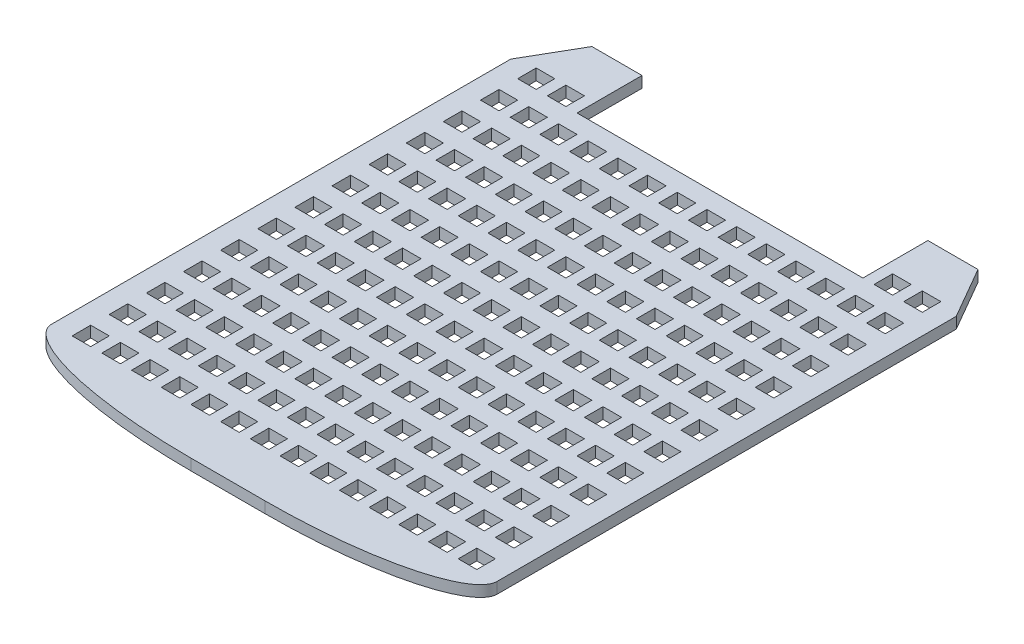
SolidWorks part; units mm, degrees
material "Balsa"
ref_plane "Front Plane" through (0, 0, 0) normal (0, 0, 1) x (1, 0, 0)
ref_plane "Top Plane" through (0, 0, 0) normal (0, 1, 0) x (1, 0, 0)
ref_plane "Right Plane" through (0, 0, 0) normal (1, 0, 0) x (0, 0, -1)
sketch "Sketch1" plane through (0, 0, 0) normal (0, 1, 0) x (1, 0, 0)
  line L1 (-60, 75) -> (60, 75)
  line L2 (-60, 75) -> (-60, -75)
  line L3 (-60, -75) -> (60, -75)
  line L4 (60, 75) -> (60, -75)
  line L5 (-60, 75) -> (60, -75) construction
  line L6 (-60, -75) -> (60, 75) construction
  point P0 (0, 0)
  dimension "D1" = 120
  dimension "D2" = 150
extrude "Boss-Extrude1" add sketch "Sketch1" along normal blind 3
sketch "Sketch2" plane through (0, 3, 0) normal (0, 1, 0) x (1, 0, 0)
  line L0 (-60, 75) -> (-60, -75) construction
  line L1 (-54.5, 62.5) -> (-49.5, 62.5)
  line L2 (-54.5, 62.5) -> (-54.5, 57.5)
  line L3 (-54.5, 57.5) -> (-49.5, 57.5)
  line L4 (-49.5, 62.5) -> (-49.5, 57.5)
  line L5 (-54.5, 62.5) -> (-49.5, 57.5) construction
  line L6 (-54.5, 57.5) -> (-49.5, 62.5) construction
  line L7 (60, 75) -> (-60, 75) construction
  line L8 (-46.5, 62.5) -> (-46.5, 57.5)
  line L9 (-46.5, 62.5) -> (-41.5, 62.5)
  line L10 (-41.5, 62.5) -> (-41.5, 57.5)
  line L11 (-46.5, 57.5) -> (-41.5, 57.5)
  line L12 (-38.5, 62.5) -> (-38.5, 57.5)
  line L13 (-38.5, 62.5) -> (-33.5, 62.5)
  line L14 (-33.5, 62.5) -> (-33.5, 57.5)
  line L15 (-38.5, 57.5) -> (-33.5, 57.5)
  line L16 (-30.5, 62.5) -> (-30.5, 57.5)
  line L17 (-30.5, 62.5) -> (-25.5, 62.5)
  line L18 (-25.5, 62.5) -> (-25.5, 57.5)
  line L19 (-30.5, 57.5) -> (-25.5, 57.5)
  line L20 (-22.5, 62.5) -> (-22.5, 57.5)
  line L21 (-22.5, 62.5) -> (-17.5, 62.5)
  line L22 (-17.5, 62.5) -> (-17.5, 57.5)
  line L23 (-22.5, 57.5) -> (-17.5, 57.5)
  line L24 (-14.5, 62.5) -> (-14.5, 57.5)
  line L25 (-14.5, 62.5) -> (-9.5, 62.5)
  line L26 (-9.5, 62.5) -> (-9.5, 57.5)
  line L27 (-14.5, 57.5) -> (-9.5, 57.5)
  line L28 (-6.5, 62.5) -> (-6.5, 57.5)
  line L29 (-6.5, 62.5) -> (-1.5, 62.5)
  line L30 (-1.5, 62.5) -> (-1.5, 57.5)
  line L31 (-6.5, 57.5) -> (-1.5, 57.5)
  line L32 (1.5, 62.5) -> (1.5, 57.5)
  line L33 (1.5, 62.5) -> (6.5, 62.5)
  line L34 (6.5, 62.5) -> (6.5, 57.5)
  line L35 (1.5, 57.5) -> (6.5, 57.5)
  line L36 (9.5, 62.5) -> (9.5, 57.5)
  line L37 (9.5, 62.5) -> (14.5, 62.5)
  line L38 (14.5, 62.5) -> (14.5, 57.5)
  line L39 (9.5, 57.5) -> (14.5, 57.5)
  line L40 (17.5, 62.5) -> (17.5, 57.5)
  line L41 (17.5, 62.5) -> (22.5, 62.5)
  line L42 (22.5, 62.5) -> (22.5, 57.5)
  line L43 (17.5, 57.5) -> (22.5, 57.5)
  line L44 (25.5, 62.5) -> (25.5, 57.5)
  line L45 (25.5, 62.5) -> (30.5, 62.5)
  line L46 (30.5, 62.5) -> (30.5, 57.5)
  line L47 (25.5, 57.5) -> (30.5, 57.5)
  line L48 (33.5, 62.5) -> (33.5, 57.5)
  line L49 (33.5, 62.5) -> (38.5, 62.5)
  line L50 (38.5, 62.5) -> (38.5, 57.5)
  line L51 (33.5, 57.5) -> (38.5, 57.5)
  line L52 (41.5, 62.5) -> (41.5, 57.5)
  line L53 (41.5, 62.5) -> (46.5, 62.5)
  line L54 (46.5, 62.5) -> (46.5, 57.5)
  line L55 (41.5, 57.5) -> (46.5, 57.5)
  line L56 (49.5, 62.5) -> (49.5, 57.5)
  line L57 (49.5, 62.5) -> (54.5, 62.5)
  line L58 (54.5, 62.5) -> (54.5, 57.5)
  line L59 (49.5, 57.5) -> (54.5, 57.5)
  line L60 (-46.5, 52.5) -> (-46.5, 47.5)
  line L61 (-46.5, 52.5) -> (-41.5, 52.5)
  line L62 (-41.5, 52.5) -> (-41.5, 47.5)
  line L63 (-46.5, 47.5) -> (-41.5, 47.5)
  line L64 (-38.5, 52.5) -> (-38.5, 47.5)
  line L65 (-38.5, 52.5) -> (-33.5, 52.5)
  line L66 (-33.5, 52.5) -> (-33.5, 47.5)
  line L67 (-38.5, 47.5) -> (-33.5, 47.5)
  line L68 (-30.5, 52.5) -> (-30.5, 47.5)
  line L69 (-30.5, 52.5) -> (-25.5, 52.5)
  line L70 (-25.5, 52.5) -> (-25.5, 47.5)
  line L71 (-30.5, 47.5) -> (-25.5, 47.5)
  line L72 (-22.5, 52.5) -> (-22.5, 47.5)
  line L73 (-22.5, 52.5) -> (-17.5, 52.5)
  line L74 (-17.5, 52.5) -> (-17.5, 47.5)
  line L75 (-22.5, 47.5) -> (-17.5, 47.5)
  line L76 (-14.5, 52.5) -> (-14.5, 47.5)
  line L77 (-14.5, 52.5) -> (-9.5, 52.5)
  line L78 (-9.5, 52.5) -> (-9.5, 47.5)
  line L79 (-14.5, 47.5) -> (-9.5, 47.5)
  line L80 (-6.5, 52.5) -> (-6.5, 47.5)
  line L81 (-6.5, 52.5) -> (-1.5, 52.5)
  line L82 (-1.5, 52.5) -> (-1.5, 47.5)
  line L83 (-6.5, 47.5) -> (-1.5, 47.5)
  line L84 (1.5, 52.5) -> (1.5, 47.5)
  line L85 (1.5, 52.5) -> (6.5, 52.5)
  line L86 (6.5, 52.5) -> (6.5, 47.5)
  line L87 (1.5, 47.5) -> (6.5, 47.5)
  line L88 (9.5, 52.5) -> (9.5, 47.5)
  line L89 (9.5, 52.5) -> (14.5, 52.5)
  line L90 (14.5, 52.5) -> (14.5, 47.5)
  line L91 (9.5, 47.5) -> (14.5, 47.5)
  line L92 (17.5, 52.5) -> (17.5, 47.5)
  line L93 (17.5, 52.5) -> (22.5, 52.5)
  line L94 (22.5, 52.5) -> (22.5, 47.5)
  line L95 (17.5, 47.5) -> (22.5, 47.5)
  line L96 (25.5, 52.5) -> (25.5, 47.5)
  line L97 (25.5, 52.5) -> (30.5, 52.5)
  line L98 (30.5, 52.5) -> (30.5, 47.5)
  line L99 (25.5, 47.5) -> (30.5, 47.5)
  line L100 (33.5, 52.5) -> (33.5, 47.5)
  line L101 (33.5, 52.5) -> (38.5, 52.5)
  line L102 (38.5, 52.5) -> (38.5, 47.5)
  line L103 (33.5, 47.5) -> (38.5, 47.5)
  line L104 (41.5, 52.5) -> (41.5, 47.5)
  line L105 (41.5, 52.5) -> (46.5, 52.5)
  line L106 (46.5, 52.5) -> (46.5, 47.5)
  line L107 (41.5, 47.5) -> (46.5, 47.5)
  line L108 (49.5, 52.5) -> (49.5, 47.5)
  line L109 (49.5, 52.5) -> (54.5, 52.5)
  line L110 (54.5, 52.5) -> (54.5, 47.5)
  line L111 (49.5, 47.5) -> (54.5, 47.5)
  line L112 (-46.5, 42.5) -> (-46.5, 37.5)
  line L113 (-46.5, 42.5) -> (-41.5, 42.5)
  line L114 (-41.5, 42.5) -> (-41.5, 37.5)
  line L115 (-46.5, 37.5) -> (-41.5, 37.5)
  line L116 (-38.5, 42.5) -> (-38.5, 37.5)
  line L117 (-38.5, 42.5) -> (-33.5, 42.5)
  line L118 (-33.5, 42.5) -> (-33.5, 37.5)
  line L119 (-38.5, 37.5) -> (-33.5, 37.5)
  line L120 (-30.5, 42.5) -> (-30.5, 37.5)
  line L121 (-30.5, 42.5) -> (-25.5, 42.5)
  line L122 (-25.5, 42.5) -> (-25.5, 37.5)
  line L123 (-30.5, 37.5) -> (-25.5, 37.5)
  line L124 (-22.5, 42.5) -> (-22.5, 37.5)
  line L125 (-22.5, 42.5) -> (-17.5, 42.5)
  line L126 (-17.5, 42.5) -> (-17.5, 37.5)
  line L127 (-22.5, 37.5) -> (-17.5, 37.5)
  line L128 (-14.5, 42.5) -> (-14.5, 37.5)
  line L129 (-14.5, 42.5) -> (-9.5, 42.5)
  line L130 (-9.5, 42.5) -> (-9.5, 37.5)
  line L131 (-14.5, 37.5) -> (-9.5, 37.5)
  line L132 (-6.5, 42.5) -> (-6.5, 37.5)
  line L133 (-6.5, 42.5) -> (-1.5, 42.5)
  line L134 (-1.5, 42.5) -> (-1.5, 37.5)
  line L135 (-6.5, 37.5) -> (-1.5, 37.5)
  line L136 (1.5, 42.5) -> (1.5, 37.5)
  line L137 (1.5, 42.5) -> (6.5, 42.5)
  line L138 (6.5, 42.5) -> (6.5, 37.5)
  line L139 (1.5, 37.5) -> (6.5, 37.5)
  line L140 (9.5, 42.5) -> (9.5, 37.5)
  line L141 (9.5, 42.5) -> (14.5, 42.5)
  line L142 (14.5, 42.5) -> (14.5, 37.5)
  line L143 (9.5, 37.5) -> (14.5, 37.5)
  line L144 (17.5, 42.5) -> (17.5, 37.5)
  line L145 (17.5, 42.5) -> (22.5, 42.5)
  line L146 (22.5, 42.5) -> (22.5, 37.5)
  line L147 (17.5, 37.5) -> (22.5, 37.5)
  line L148 (25.5, 42.5) -> (25.5, 37.5)
  line L149 (25.5, 42.5) -> (30.5, 42.5)
  line L150 (30.5, 42.5) -> (30.5, 37.5)
  line L151 (25.5, 37.5) -> (30.5, 37.5)
  line L152 (33.5, 42.5) -> (33.5, 37.5)
  line L153 (33.5, 42.5) -> (38.5, 42.5)
  line L154 (38.5, 42.5) -> (38.5, 37.5)
  line L155 (33.5, 37.5) -> (38.5, 37.5)
  line L156 (41.5, 42.5) -> (41.5, 37.5)
  line L157 (41.5, 42.5) -> (46.5, 42.5)
  line L158 (46.5, 42.5) -> (46.5, 37.5)
  line L159 (41.5, 37.5) -> (46.5, 37.5)
  line L160 (49.5, 42.5) -> (49.5, 37.5)
  line L161 (49.5, 42.5) -> (54.5, 42.5)
  line L162 (54.5, 42.5) -> (54.5, 37.5)
  line L163 (49.5, 37.5) -> (54.5, 37.5)
  line L164 (-46.5, 32.5) -> (-46.5, 27.5)
  line L165 (-46.5, 32.5) -> (-41.5, 32.5)
  line L166 (-41.5, 32.5) -> (-41.5, 27.5)
  line L167 (-46.5, 27.5) -> (-41.5, 27.5)
  line L168 (-38.5, 32.5) -> (-38.5, 27.5)
  line L169 (-38.5, 32.5) -> (-33.5, 32.5)
  line L170 (-33.5, 32.5) -> (-33.5, 27.5)
  line L171 (-38.5, 27.5) -> (-33.5, 27.5)
  line L172 (-30.5, 32.5) -> (-30.5, 27.5)
  line L173 (-30.5, 32.5) -> (-25.5, 32.5)
  line L174 (-25.5, 32.5) -> (-25.5, 27.5)
  line L175 (-30.5, 27.5) -> (-25.5, 27.5)
  line L176 (-22.5, 32.5) -> (-22.5, 27.5)
  line L177 (-22.5, 32.5) -> (-17.5, 32.5)
  line L178 (-17.5, 32.5) -> (-17.5, 27.5)
  line L179 (-22.5, 27.5) -> (-17.5, 27.5)
  line L180 (-14.5, 32.5) -> (-14.5, 27.5)
  line L181 (-14.5, 32.5) -> (-9.5, 32.5)
  line L182 (-9.5, 32.5) -> (-9.5, 27.5)
  line L183 (-14.5, 27.5) -> (-9.5, 27.5)
  line L184 (-6.5, 32.5) -> (-6.5, 27.5)
  line L185 (-6.5, 32.5) -> (-1.5, 32.5)
  line L186 (-1.5, 32.5) -> (-1.5, 27.5)
  line L187 (-6.5, 27.5) -> (-1.5, 27.5)
  line L188 (1.5, 32.5) -> (1.5, 27.5)
  line L189 (1.5, 32.5) -> (6.5, 32.5)
  line L190 (6.5, 32.5) -> (6.5, 27.5)
  line L191 (1.5, 27.5) -> (6.5, 27.5)
  line L192 (9.5, 32.5) -> (9.5, 27.5)
  line L193 (9.5, 32.5) -> (14.5, 32.5)
  line L194 (14.5, 32.5) -> (14.5, 27.5)
  line L195 (9.5, 27.5) -> (14.5, 27.5)
  line L196 (17.5, 32.5) -> (17.5, 27.5)
  line L197 (17.5, 32.5) -> (22.5, 32.5)
  line L198 (22.5, 32.5) -> (22.5, 27.5)
  line L199 (17.5, 27.5) -> (22.5, 27.5)
  line L200 (25.5, 32.5) -> (25.5, 27.5)
  line L201 (25.5, 32.5) -> (30.5, 32.5)
  line L202 (30.5, 32.5) -> (30.5, 27.5)
  line L203 (25.5, 27.5) -> (30.5, 27.5)
  line L204 (33.5, 32.5) -> (33.5, 27.5)
  line L205 (33.5, 32.5) -> (38.5, 32.5)
  line L206 (38.5, 32.5) -> (38.5, 27.5)
  line L207 (33.5, 27.5) -> (38.5, 27.5)
  line L208 (41.5, 32.5) -> (41.5, 27.5)
  line L209 (41.5, 32.5) -> (46.5, 32.5)
  line L210 (46.5, 32.5) -> (46.5, 27.5)
  line L211 (41.5, 27.5) -> (46.5, 27.5)
  line L212 (49.5, 32.5) -> (49.5, 27.5)
  line L213 (49.5, 32.5) -> (54.5, 32.5)
  line L214 (54.5, 32.5) -> (54.5, 27.5)
  line L215 (49.5, 27.5) -> (54.5, 27.5)
  line L216 (-46.5, 22.5) -> (-46.5, 17.5)
  line L217 (-46.5, 22.5) -> (-41.5, 22.5)
  line L218 (-41.5, 22.5) -> (-41.5, 17.5)
  line L219 (-46.5, 17.5) -> (-41.5, 17.5)
  line L220 (-38.5, 22.5) -> (-38.5, 17.5)
  line L221 (-38.5, 22.5) -> (-33.5, 22.5)
  line L222 (-33.5, 22.5) -> (-33.5, 17.5)
  line L223 (-38.5, 17.5) -> (-33.5, 17.5)
  line L224 (-30.5, 22.5) -> (-30.5, 17.5)
  line L225 (-30.5, 22.5) -> (-25.5, 22.5)
  line L226 (-25.5, 22.5) -> (-25.5, 17.5)
  line L227 (-30.5, 17.5) -> (-25.5, 17.5)
  line L228 (-22.5, 22.5) -> (-22.5, 17.5)
  line L229 (-22.5, 22.5) -> (-17.5, 22.5)
  line L230 (-17.5, 22.5) -> (-17.5, 17.5)
  line L231 (-22.5, 17.5) -> (-17.5, 17.5)
  line L232 (-14.5, 22.5) -> (-14.5, 17.5)
  line L233 (-14.5, 22.5) -> (-9.5, 22.5)
  line L234 (-9.5, 22.5) -> (-9.5, 17.5)
  line L235 (-14.5, 17.5) -> (-9.5, 17.5)
  line L236 (-6.5, 22.5) -> (-6.5, 17.5)
  line L237 (-6.5, 22.5) -> (-1.5, 22.5)
  line L238 (-1.5, 22.5) -> (-1.5, 17.5)
  line L239 (-6.5, 17.5) -> (-1.5, 17.5)
  line L240 (1.5, 22.5) -> (1.5, 17.5)
  line L241 (1.5, 22.5) -> (6.5, 22.5)
  line L242 (6.5, 22.5) -> (6.5, 17.5)
  line L243 (1.5, 17.5) -> (6.5, 17.5)
  line L244 (9.5, 22.5) -> (9.5, 17.5)
  line L245 (9.5, 22.5) -> (14.5, 22.5)
  line L246 (14.5, 22.5) -> (14.5, 17.5)
  line L247 (9.5, 17.5) -> (14.5, 17.5)
  line L248 (17.5, 22.5) -> (17.5, 17.5)
  line L249 (17.5, 22.5) -> (22.5, 22.5)
  line L250 (22.5, 22.5) -> (22.5, 17.5)
  line L251 (17.5, 17.5) -> (22.5, 17.5)
  line L252 (25.5, 22.5) -> (25.5, 17.5)
  line L253 (25.5, 22.5) -> (30.5, 22.5)
  line L254 (30.5, 22.5) -> (30.5, 17.5)
  line L255 (25.5, 17.5) -> (30.5, 17.5)
  line L256 (33.5, 22.5) -> (33.5, 17.5)
  line L257 (33.5, 22.5) -> (38.5, 22.5)
  line L258 (38.5, 22.5) -> (38.5, 17.5)
  line L259 (33.5, 17.5) -> (38.5, 17.5)
  line L260 (41.5, 22.5) -> (41.5, 17.5)
  line L261 (41.5, 22.5) -> (46.5, 22.5)
  line L262 (46.5, 22.5) -> (46.5, 17.5)
  line L263 (41.5, 17.5) -> (46.5, 17.5)
  line L264 (49.5, 22.5) -> (49.5, 17.5)
  line L265 (49.5, 22.5) -> (54.5, 22.5)
  line L266 (54.5, 22.5) -> (54.5, 17.5)
  line L267 (49.5, 17.5) -> (54.5, 17.5)
  line L268 (-46.5, 12.5) -> (-46.5, 7.5)
  line L269 (-46.5, 12.5) -> (-41.5, 12.5)
  line L270 (-41.5, 12.5) -> (-41.5, 7.5)
  line L271 (-46.5, 7.5) -> (-41.5, 7.5)
  line L272 (-38.5, 12.5) -> (-38.5, 7.5)
  line L273 (-38.5, 12.5) -> (-33.5, 12.5)
  line L274 (-33.5, 12.5) -> (-33.5, 7.5)
  line L275 (-38.5, 7.5) -> (-33.5, 7.5)
  line L276 (-30.5, 12.5) -> (-30.5, 7.5)
  line L277 (-30.5, 12.5) -> (-25.5, 12.5)
  line L278 (-25.5, 12.5) -> (-25.5, 7.5)
  line L279 (-30.5, 7.5) -> (-25.5, 7.5)
  line L280 (-22.5, 12.5) -> (-22.5, 7.5)
  line L281 (-22.5, 12.5) -> (-17.5, 12.5)
  line L282 (-17.5, 12.5) -> (-17.5, 7.5)
  line L283 (-22.5, 7.5) -> (-17.5, 7.5)
  line L284 (-14.5, 12.5) -> (-14.5, 7.5)
  line L285 (-14.5, 12.5) -> (-9.5, 12.5)
  line L286 (-9.5, 12.5) -> (-9.5, 7.5)
  line L287 (-14.5, 7.5) -> (-9.5, 7.5)
  line L288 (-6.5, 12.5) -> (-6.5, 7.5)
  line L289 (-6.5, 12.5) -> (-1.5, 12.5)
  line L290 (-1.5, 12.5) -> (-1.5, 7.5)
  line L291 (-6.5, 7.5) -> (-1.5, 7.5)
  line L292 (1.5, 12.5) -> (1.5, 7.5)
  line L293 (1.5, 12.5) -> (6.5, 12.5)
  line L294 (6.5, 12.5) -> (6.5, 7.5)
  line L295 (1.5, 7.5) -> (6.5, 7.5)
  line L296 (9.5, 12.5) -> (9.5, 7.5)
  line L297 (9.5, 12.5) -> (14.5, 12.5)
  line L298 (14.5, 12.5) -> (14.5, 7.5)
  line L299 (9.5, 7.5) -> (14.5, 7.5)
  line L300 (17.5, 12.5) -> (17.5, 7.5)
  line L301 (17.5, 12.5) -> (22.5, 12.5)
  line L302 (22.5, 12.5) -> (22.5, 7.5)
  line L303 (17.5, 7.5) -> (22.5, 7.5)
  line L304 (25.5, 12.5) -> (25.5, 7.5)
  line L305 (25.5, 12.5) -> (30.5, 12.5)
  line L306 (30.5, 12.5) -> (30.5, 7.5)
  line L307 (25.5, 7.5) -> (30.5, 7.5)
  line L308 (33.5, 12.5) -> (33.5, 7.5)
  line L309 (33.5, 12.5) -> (38.5, 12.5)
  line L310 (38.5, 12.5) -> (38.5, 7.5)
  line L311 (33.5, 7.5) -> (38.5, 7.5)
  line L312 (41.5, 12.5) -> (41.5, 7.5)
  line L313 (41.5, 12.5) -> (46.5, 12.5)
  line L314 (46.5, 12.5) -> (46.5, 7.5)
  line L315 (41.5, 7.5) -> (46.5, 7.5)
  line L316 (49.5, 12.5) -> (49.5, 7.5)
  line L317 (49.5, 12.5) -> (54.5, 12.5)
  line L318 (54.5, 12.5) -> (54.5, 7.5)
  line L319 (49.5, 7.5) -> (54.5, 7.5)
  line L320 (-46.5, 2.5) -> (-46.5, -2.5)
  line L321 (-46.5, 2.5) -> (-41.5, 2.5)
  line L322 (-41.5, 2.5) -> (-41.5, -2.5)
  line L323 (-46.5, -2.5) -> (-41.5, -2.5)
  line L324 (-38.5, 2.5) -> (-38.5, -2.5)
  line L325 (-38.5, 2.5) -> (-33.5, 2.5)
  line L326 (-33.5, 2.5) -> (-33.5, -2.5)
  line L327 (-38.5, -2.5) -> (-33.5, -2.5)
  line L328 (-30.5, 2.5) -> (-30.5, -2.5)
  line L329 (-30.5, 2.5) -> (-25.5, 2.5)
  line L330 (-25.5, 2.5) -> (-25.5, -2.5)
  line L331 (-30.5, -2.5) -> (-25.5, -2.5)
  line L332 (-22.5, 2.5) -> (-22.5, -2.5)
  line L333 (-22.5, 2.5) -> (-17.5, 2.5)
  line L334 (-17.5, 2.5) -> (-17.5, -2.5)
  line L335 (-22.5, -2.5) -> (-17.5, -2.5)
  line L336 (-14.5, 2.5) -> (-14.5, -2.5)
  line L337 (-14.5, 2.5) -> (-9.5, 2.5)
  line L338 (-9.5, 2.5) -> (-9.5, -2.5)
  line L339 (-14.5, -2.5) -> (-9.5, -2.5)
  line L340 (-6.5, 2.5) -> (-6.5, -2.5)
  line L341 (-6.5, 2.5) -> (-1.5, 2.5)
  line L342 (-1.5, 2.5) -> (-1.5, -2.5)
  line L343 (-6.5, -2.5) -> (-1.5, -2.5)
  line L344 (1.5, 2.5) -> (1.5, -2.5)
  line L345 (1.5, 2.5) -> (6.5, 2.5)
  line L346 (6.5, 2.5) -> (6.5, -2.5)
  line L347 (1.5, -2.5) -> (6.5, -2.5)
  line L348 (9.5, 2.5) -> (9.5, -2.5)
  line L349 (9.5, 2.5) -> (14.5, 2.5)
  line L350 (14.5, 2.5) -> (14.5, -2.5)
  line L351 (9.5, -2.5) -> (14.5, -2.5)
  line L352 (17.5, 2.5) -> (17.5, -2.5)
  line L353 (17.5, 2.5) -> (22.5, 2.5)
  line L354 (22.5, 2.5) -> (22.5, -2.5)
  line L355 (17.5, -2.5) -> (22.5, -2.5)
  line L356 (25.5, 2.5) -> (25.5, -2.5)
  line L357 (25.5, 2.5) -> (30.5, 2.5)
  line L358 (30.5, 2.5) -> (30.5, -2.5)
  line L359 (25.5, -2.5) -> (30.5, -2.5)
  line L360 (33.5, 2.5) -> (33.5, -2.5)
  line L361 (33.5, 2.5) -> (38.5, 2.5)
  line L362 (38.5, 2.5) -> (38.5, -2.5)
  line L363 (33.5, -2.5) -> (38.5, -2.5)
  line L364 (41.5, 2.5) -> (41.5, -2.5)
  line L365 (41.5, 2.5) -> (46.5, 2.5)
  line L366 (46.5, 2.5) -> (46.5, -2.5)
  line L367 (41.5, -2.5) -> (46.5, -2.5)
  line L368 (49.5, 2.5) -> (49.5, -2.5)
  line L369 (49.5, 2.5) -> (54.5, 2.5)
  line L370 (54.5, 2.5) -> (54.5, -2.5)
  line L371 (49.5, -2.5) -> (54.5, -2.5)
  line L372 (-46.5, -7.5) -> (-46.5, -12.5)
  line L373 (-46.5, -7.5) -> (-41.5, -7.5)
  line L374 (-41.5, -7.5) -> (-41.5, -12.5)
  line L375 (-46.5, -12.5) -> (-41.5, -12.5)
  line L376 (-38.5, -7.5) -> (-38.5, -12.5)
  line L377 (-38.5, -7.5) -> (-33.5, -7.5)
  line L378 (-33.5, -7.5) -> (-33.5, -12.5)
  line L379 (-38.5, -12.5) -> (-33.5, -12.5)
  line L380 (-30.5, -7.5) -> (-30.5, -12.5)
  line L381 (-30.5, -7.5) -> (-25.5, -7.5)
  line L382 (-25.5, -7.5) -> (-25.5, -12.5)
  line L383 (-30.5, -12.5) -> (-25.5, -12.5)
  line L384 (-22.5, -7.5) -> (-22.5, -12.5)
  line L385 (-22.5, -7.5) -> (-17.5, -7.5)
  line L386 (-17.5, -7.5) -> (-17.5, -12.5)
  line L387 (-22.5, -12.5) -> (-17.5, -12.5)
  line L388 (-14.5, -7.5) -> (-14.5, -12.5)
  line L389 (-14.5, -7.5) -> (-9.5, -7.5)
  line L390 (-9.5, -7.5) -> (-9.5, -12.5)
  line L391 (-14.5, -12.5) -> (-9.5, -12.5)
  line L392 (-6.5, -7.5) -> (-6.5, -12.5)
  line L393 (-6.5, -7.5) -> (-1.5, -7.5)
  line L394 (-1.5, -7.5) -> (-1.5, -12.5)
  line L395 (-6.5, -12.5) -> (-1.5, -12.5)
  line L396 (1.5, -7.5) -> (1.5, -12.5)
  line L397 (1.5, -7.5) -> (6.5, -7.5)
  line L398 (6.5, -7.5) -> (6.5, -12.5)
  line L399 (1.5, -12.5) -> (6.5, -12.5)
  line L400 (9.5, -7.5) -> (9.5, -12.5)
  line L401 (9.5, -7.5) -> (14.5, -7.5)
  line L402 (14.5, -7.5) -> (14.5, -12.5)
  line L403 (9.5, -12.5) -> (14.5, -12.5)
  line L404 (17.5, -7.5) -> (17.5, -12.5)
  line L405 (17.5, -7.5) -> (22.5, -7.5)
  line L406 (22.5, -7.5) -> (22.5, -12.5)
  line L407 (17.5, -12.5) -> (22.5, -12.5)
  line L408 (25.5, -7.5) -> (25.5, -12.5)
  line L409 (25.5, -7.5) -> (30.5, -7.5)
  line L410 (30.5, -7.5) -> (30.5, -12.5)
  line L411 (25.5, -12.5) -> (30.5, -12.5)
  line L412 (33.5, -7.5) -> (33.5, -12.5)
  line L413 (33.5, -7.5) -> (38.5, -7.5)
  line L414 (38.5, -7.5) -> (38.5, -12.5)
  line L415 (33.5, -12.5) -> (38.5, -12.5)
  line L416 (41.5, -7.5) -> (41.5, -12.5)
  line L417 (41.5, -7.5) -> (46.5, -7.5)
  line L418 (46.5, -7.5) -> (46.5, -12.5)
  line L419 (41.5, -12.5) -> (46.5, -12.5)
  line L420 (49.5, -7.5) -> (49.5, -12.5)
  line L421 (49.5, -7.5) -> (54.5, -7.5)
  line L422 (54.5, -7.5) -> (54.5, -12.5)
  line L423 (49.5, -12.5) -> (54.5, -12.5)
  line L424 (-46.5, -17.5) -> (-46.5, -22.5)
  line L425 (-46.5, -17.5) -> (-41.5, -17.5)
  line L426 (-41.5, -17.5) -> (-41.5, -22.5)
  line L427 (-46.5, -22.5) -> (-41.5, -22.5)
  line L428 (-38.5, -17.5) -> (-38.5, -22.5)
  line L429 (-38.5, -17.5) -> (-33.5, -17.5)
  line L430 (-33.5, -17.5) -> (-33.5, -22.5)
  line L431 (-38.5, -22.5) -> (-33.5, -22.5)
  line L432 (-30.5, -17.5) -> (-30.5, -22.5)
  line L433 (-30.5, -17.5) -> (-25.5, -17.5)
  line L434 (-25.5, -17.5) -> (-25.5, -22.5)
  line L435 (-30.5, -22.5) -> (-25.5, -22.5)
  line L436 (-22.5, -17.5) -> (-22.5, -22.5)
  line L437 (-22.5, -17.5) -> (-17.5, -17.5)
  line L438 (-17.5, -17.5) -> (-17.5, -22.5)
  line L439 (-22.5, -22.5) -> (-17.5, -22.5)
  line L440 (-14.5, -17.5) -> (-14.5, -22.5)
  line L441 (-14.5, -17.5) -> (-9.5, -17.5)
  line L442 (-9.5, -17.5) -> (-9.5, -22.5)
  line L443 (-14.5, -22.5) -> (-9.5, -22.5)
  line L444 (-6.5, -17.5) -> (-6.5, -22.5)
  line L445 (-6.5, -17.5) -> (-1.5, -17.5)
  line L446 (-1.5, -17.5) -> (-1.5, -22.5)
  line L447 (-6.5, -22.5) -> (-1.5, -22.5)
  line L448 (1.5, -17.5) -> (1.5, -22.5)
  line L449 (1.5, -17.5) -> (6.5, -17.5)
  line L450 (6.5, -17.5) -> (6.5, -22.5)
  line L451 (1.5, -22.5) -> (6.5, -22.5)
  line L452 (9.5, -17.5) -> (9.5, -22.5)
  line L453 (9.5, -17.5) -> (14.5, -17.5)
  line L454 (14.5, -17.5) -> (14.5, -22.5)
  line L455 (9.5, -22.5) -> (14.5, -22.5)
  line L456 (17.5, -17.5) -> (17.5, -22.5)
  line L457 (17.5, -17.5) -> (22.5, -17.5)
  line L458 (22.5, -17.5) -> (22.5, -22.5)
  line L459 (17.5, -22.5) -> (22.5, -22.5)
  line L460 (25.5, -17.5) -> (25.5, -22.5)
  line L461 (25.5, -17.5) -> (30.5, -17.5)
  line L462 (30.5, -17.5) -> (30.5, -22.5)
  line L463 (25.5, -22.5) -> (30.5, -22.5)
  line L464 (33.5, -17.5) -> (33.5, -22.5)
  line L465 (33.5, -17.5) -> (38.5, -17.5)
  line L466 (38.5, -17.5) -> (38.5, -22.5)
  line L467 (33.5, -22.5) -> (38.5, -22.5)
  line L468 (41.5, -17.5) -> (41.5, -22.5)
  line L469 (41.5, -17.5) -> (46.5, -17.5)
  line L470 (46.5, -17.5) -> (46.5, -22.5)
  line L471 (41.5, -22.5) -> (46.5, -22.5)
  line L472 (49.5, -17.5) -> (49.5, -22.5)
  line L473 (49.5, -17.5) -> (54.5, -17.5)
  line L474 (54.5, -17.5) -> (54.5, -22.5)
  line L475 (49.5, -22.5) -> (54.5, -22.5)
  line L476 (-46.5, -27.5) -> (-46.5, -32.5)
  line L477 (-46.5, -27.5) -> (-41.5, -27.5)
  line L478 (-41.5, -27.5) -> (-41.5, -32.5)
  line L479 (-46.5, -32.5) -> (-41.5, -32.5)
  line L480 (-38.5, -27.5) -> (-38.5, -32.5)
  line L481 (-38.5, -27.5) -> (-33.5, -27.5)
  line L482 (-33.5, -27.5) -> (-33.5, -32.5)
  line L483 (-38.5, -32.5) -> (-33.5, -32.5)
  line L484 (-30.5, -27.5) -> (-30.5, -32.5)
  line L485 (-30.5, -27.5) -> (-25.5, -27.5)
  line L486 (-25.5, -27.5) -> (-25.5, -32.5)
  line L487 (-30.5, -32.5) -> (-25.5, -32.5)
  line L488 (-22.5, -27.5) -> (-22.5, -32.5)
  line L489 (-22.5, -27.5) -> (-17.5, -27.5)
  line L490 (-17.5, -27.5) -> (-17.5, -32.5)
  line L491 (-22.5, -32.5) -> (-17.5, -32.5)
  line L492 (-14.5, -27.5) -> (-14.5, -32.5)
  line L493 (-14.5, -27.5) -> (-9.5, -27.5)
  line L494 (-9.5, -27.5) -> (-9.5, -32.5)
  line L495 (-14.5, -32.5) -> (-9.5, -32.5)
  line L496 (-6.5, -27.5) -> (-6.5, -32.5)
  line L497 (-6.5, -27.5) -> (-1.5, -27.5)
  line L498 (-1.5, -27.5) -> (-1.5, -32.5)
  line L499 (-6.5, -32.5) -> (-1.5, -32.5)
  line L500 (1.5, -27.5) -> (1.5, -32.5)
  line L501 (1.5, -27.5) -> (6.5, -27.5)
  line L502 (6.5, -27.5) -> (6.5, -32.5)
  line L503 (1.5, -32.5) -> (6.5, -32.5)
  line L504 (9.5, -27.5) -> (9.5, -32.5)
  line L505 (9.5, -27.5) -> (14.5, -27.5)
  line L506 (14.5, -27.5) -> (14.5, -32.5)
  line L507 (9.5, -32.5) -> (14.5, -32.5)
  line L508 (17.5, -27.5) -> (17.5, -32.5)
  line L509 (17.5, -27.5) -> (22.5, -27.5)
  line L510 (22.5, -27.5) -> (22.5, -32.5)
  line L511 (17.5, -32.5) -> (22.5, -32.5)
  line L512 (25.5, -27.5) -> (25.5, -32.5)
  line L513 (25.5, -27.5) -> (30.5, -27.5)
  line L514 (30.5, -27.5) -> (30.5, -32.5)
  line L515 (25.5, -32.5) -> (30.5, -32.5)
  line L516 (33.5, -27.5) -> (33.5, -32.5)
  line L517 (33.5, -27.5) -> (38.5, -27.5)
  line L518 (38.5, -27.5) -> (38.5, -32.5)
  line L519 (33.5, -32.5) -> (38.5, -32.5)
  line L520 (41.5, -27.5) -> (41.5, -32.5)
  line L521 (41.5, -27.5) -> (46.5, -27.5)
  line L522 (46.5, -27.5) -> (46.5, -32.5)
  line L523 (41.5, -32.5) -> (46.5, -32.5)
  line L524 (49.5, -27.5) -> (49.5, -32.5)
  line L525 (49.5, -27.5) -> (54.5, -27.5)
  line L526 (54.5, -27.5) -> (54.5, -32.5)
  line L527 (49.5, -32.5) -> (54.5, -32.5)
  line L528 (-46.5, -37.5) -> (-46.5, -42.5)
  line L529 (-46.5, -37.5) -> (-41.5, -37.5)
  line L530 (-41.5, -37.5) -> (-41.5, -42.5)
  line L531 (-46.5, -42.5) -> (-41.5, -42.5)
  line L532 (-38.5, -37.5) -> (-38.5, -42.5)
  line L533 (-38.5, -37.5) -> (-33.5, -37.5)
  line L534 (-33.5, -37.5) -> (-33.5, -42.5)
  line L535 (-38.5, -42.5) -> (-33.5, -42.5)
  line L536 (-30.5, -37.5) -> (-30.5, -42.5)
  line L537 (-30.5, -37.5) -> (-25.5, -37.5)
  line L538 (-25.5, -37.5) -> (-25.5, -42.5)
  line L539 (-30.5, -42.5) -> (-25.5, -42.5)
  line L540 (-22.5, -37.5) -> (-22.5, -42.5)
  line L541 (-22.5, -37.5) -> (-17.5, -37.5)
  line L542 (-17.5, -37.5) -> (-17.5, -42.5)
  line L543 (-22.5, -42.5) -> (-17.5, -42.5)
  line L544 (-14.5, -37.5) -> (-14.5, -42.5)
  line L545 (-14.5, -37.5) -> (-9.5, -37.5)
  line L546 (-9.5, -37.5) -> (-9.5, -42.5)
  line L547 (-14.5, -42.5) -> (-9.5, -42.5)
  line L548 (-6.5, -37.5) -> (-6.5, -42.5)
  line L549 (-6.5, -37.5) -> (-1.5, -37.5)
  line L550 (-1.5, -37.5) -> (-1.5, -42.5)
  line L551 (-6.5, -42.5) -> (-1.5, -42.5)
  line L552 (1.5, -37.5) -> (1.5, -42.5)
  line L553 (1.5, -37.5) -> (6.5, -37.5)
  line L554 (6.5, -37.5) -> (6.5, -42.5)
  line L555 (1.5, -42.5) -> (6.5, -42.5)
  line L556 (9.5, -37.5) -> (9.5, -42.5)
  line L557 (9.5, -37.5) -> (14.5, -37.5)
  line L558 (14.5, -37.5) -> (14.5, -42.5)
  line L559 (9.5, -42.5) -> (14.5, -42.5)
  line L560 (17.5, -37.5) -> (17.5, -42.5)
  line L561 (17.5, -37.5) -> (22.5, -37.5)
  line L562 (22.5, -37.5) -> (22.5, -42.5)
  line L563 (17.5, -42.5) -> (22.5, -42.5)
  line L564 (25.5, -37.5) -> (25.5, -42.5)
  line L565 (25.5, -37.5) -> (30.5, -37.5)
  line L566 (30.5, -37.5) -> (30.5, -42.5)
  line L567 (25.5, -42.5) -> (30.5, -42.5)
  line L568 (33.5, -37.5) -> (33.5, -42.5)
  line L569 (33.5, -37.5) -> (38.5, -37.5)
  line L570 (38.5, -37.5) -> (38.5, -42.5)
  line L571 (33.5, -42.5) -> (38.5, -42.5)
  line L572 (41.5, -37.5) -> (41.5, -42.5)
  line L573 (41.5, -37.5) -> (46.5, -37.5)
  line L574 (46.5, -37.5) -> (46.5, -42.5)
  line L575 (41.5, -42.5) -> (46.5, -42.5)
  line L576 (49.5, -37.5) -> (49.5, -42.5)
  line L577 (49.5, -37.5) -> (54.5, -37.5)
  line L578 (54.5, -37.5) -> (54.5, -42.5)
  line L579 (49.5, -42.5) -> (54.5, -42.5)
  line L580 (-46.5, -47.5) -> (-46.5, -52.5)
  line L581 (-46.5, -47.5) -> (-41.5, -47.5)
  line L582 (-41.5, -47.5) -> (-41.5, -52.5)
  line L583 (-46.5, -52.5) -> (-41.5, -52.5)
  line L584 (-38.5, -47.5) -> (-38.5, -52.5)
  line L585 (-38.5, -47.5) -> (-33.5, -47.5)
  line L586 (-33.5, -47.5) -> (-33.5, -52.5)
  line L587 (-38.5, -52.5) -> (-33.5, -52.5)
  line L588 (-30.5, -47.5) -> (-30.5, -52.5)
  line L589 (-30.5, -47.5) -> (-25.5, -47.5)
  line L590 (-25.5, -47.5) -> (-25.5, -52.5)
  line L591 (-30.5, -52.5) -> (-25.5, -52.5)
  line L592 (-22.5, -47.5) -> (-22.5, -52.5)
  line L593 (-22.5, -47.5) -> (-17.5, -47.5)
  line L594 (-17.5, -47.5) -> (-17.5, -52.5)
  line L595 (-22.5, -52.5) -> (-17.5, -52.5)
  line L596 (-14.5, -47.5) -> (-14.5, -52.5)
  line L597 (-14.5, -47.5) -> (-9.5, -47.5)
  line L598 (-9.5, -47.5) -> (-9.5, -52.5)
  line L599 (-14.5, -52.5) -> (-9.5, -52.5)
  line L600 (-6.5, -47.5) -> (-6.5, -52.5)
  line L601 (-6.5, -47.5) -> (-1.5, -47.5)
  line L602 (-1.5, -47.5) -> (-1.5, -52.5)
  line L603 (-6.5, -52.5) -> (-1.5, -52.5)
  line L604 (1.5, -47.5) -> (1.5, -52.5)
  line L605 (1.5, -47.5) -> (6.5, -47.5)
  line L606 (6.5, -47.5) -> (6.5, -52.5)
  line L607 (1.5, -52.5) -> (6.5, -52.5)
  line L608 (9.5, -47.5) -> (9.5, -52.5)
  line L609 (9.5, -47.5) -> (14.5, -47.5)
  line L610 (14.5, -47.5) -> (14.5, -52.5)
  line L611 (9.5, -52.5) -> (14.5, -52.5)
  line L612 (17.5, -47.5) -> (17.5, -52.5)
  line L613 (17.5, -47.5) -> (22.5, -47.5)
  line L614 (22.5, -47.5) -> (22.5, -52.5)
  line L615 (17.5, -52.5) -> (22.5, -52.5)
  line L616 (25.5, -47.5) -> (25.5, -52.5)
  line L617 (25.5, -47.5) -> (30.5, -47.5)
  line L618 (30.5, -47.5) -> (30.5, -52.5)
  line L619 (25.5, -52.5) -> (30.5, -52.5)
  line L620 (33.5, -47.5) -> (33.5, -52.5)
  line L621 (33.5, -47.5) -> (38.5, -47.5)
  line L622 (38.5, -47.5) -> (38.5, -52.5)
  line L623 (33.5, -52.5) -> (38.5, -52.5)
  line L624 (41.5, -47.5) -> (41.5, -52.5)
  line L625 (41.5, -47.5) -> (46.5, -47.5)
  line L626 (46.5, -47.5) -> (46.5, -52.5)
  line L627 (41.5, -52.5) -> (46.5, -52.5)
  line L628 (49.5, -47.5) -> (49.5, -52.5)
  line L629 (49.5, -47.5) -> (54.5, -47.5)
  line L630 (54.5, -47.5) -> (54.5, -52.5)
  line L631 (49.5, -52.5) -> (54.5, -52.5)
  line L632 (-46.5, -57.5) -> (-46.5, -62.5)
  line L633 (-46.5, -57.5) -> (-41.5, -57.5)
  line L634 (-41.5, -57.5) -> (-41.5, -62.5)
  line L635 (-46.5, -62.5) -> (-41.5, -62.5)
  line L636 (-38.5, -57.5) -> (-38.5, -62.5)
  line L637 (-38.5, -57.5) -> (-33.5, -57.5)
  line L638 (-33.5, -57.5) -> (-33.5, -62.5)
  line L639 (-38.5, -62.5) -> (-33.5, -62.5)
  line L640 (-30.5, -57.5) -> (-30.5, -62.5)
  line L641 (-30.5, -57.5) -> (-25.5, -57.5)
  line L642 (-25.5, -57.5) -> (-25.5, -62.5)
  line L643 (-30.5, -62.5) -> (-25.5, -62.5)
  line L644 (-22.5, -57.5) -> (-22.5, -62.5)
  line L645 (-22.5, -57.5) -> (-17.5, -57.5)
  line L646 (-17.5, -57.5) -> (-17.5, -62.5)
  line L647 (-22.5, -62.5) -> (-17.5, -62.5)
  line L648 (-14.5, -57.5) -> (-14.5, -62.5)
  line L649 (-14.5, -57.5) -> (-9.5, -57.5)
  line L650 (-9.5, -57.5) -> (-9.5, -62.5)
  line L651 (-14.5, -62.5) -> (-9.5, -62.5)
  line L652 (-6.5, -57.5) -> (-6.5, -62.5)
  line L653 (-6.5, -57.5) -> (-1.5, -57.5)
  line L654 (-1.5, -57.5) -> (-1.5, -62.5)
  line L655 (-6.5, -62.5) -> (-1.5, -62.5)
  line L656 (1.5, -57.5) -> (1.5, -62.5)
  line L657 (1.5, -57.5) -> (6.5, -57.5)
  line L658 (6.5, -57.5) -> (6.5, -62.5)
  line L659 (1.5, -62.5) -> (6.5, -62.5)
  line L660 (9.5, -57.5) -> (9.5, -62.5)
  line L661 (9.5, -57.5) -> (14.5, -57.5)
  line L662 (14.5, -57.5) -> (14.5, -62.5)
  line L663 (9.5, -62.5) -> (14.5, -62.5)
  line L664 (17.5, -57.5) -> (17.5, -62.5)
  line L665 (17.5, -57.5) -> (22.5, -57.5)
  line L666 (22.5, -57.5) -> (22.5, -62.5)
  line L667 (17.5, -62.5) -> (22.5, -62.5)
  line L668 (25.5, -57.5) -> (25.5, -62.5)
  line L669 (25.5, -57.5) -> (30.5, -57.5)
  line L670 (30.5, -57.5) -> (30.5, -62.5)
  line L671 (25.5, -62.5) -> (30.5, -62.5)
  line L672 (33.5, -57.5) -> (33.5, -62.5)
  line L673 (33.5, -57.5) -> (38.5, -57.5)
  line L674 (38.5, -57.5) -> (38.5, -62.5)
  line L675 (33.5, -62.5) -> (38.5, -62.5)
  line L676 (41.5, -57.5) -> (41.5, -62.5)
  line L677 (41.5, -57.5) -> (46.5, -57.5)
  line L678 (46.5, -57.5) -> (46.5, -62.5)
  line L679 (41.5, -62.5) -> (46.5, -62.5)
  line L680 (49.5, -57.5) -> (49.5, -62.5)
  line L681 (49.5, -57.5) -> (54.5, -57.5)
  line L682 (54.5, -57.5) -> (54.5, -62.5)
  line L683 (49.5, -62.5) -> (54.5, -62.5)
  line L684 (-54.5, 52.5) -> (-54.5, 47.5)
  line L685 (-54.5, 52.5) -> (-49.5, 52.5)
  line L686 (-49.5, 52.5) -> (-49.5, 47.5)
  line L687 (-54.5, 47.5) -> (-49.5, 47.5)
  line L688 (-54.5, 42.5) -> (-54.5, 37.5)
  line L689 (-54.5, 42.5) -> (-49.5, 42.5)
  line L690 (-49.5, 42.5) -> (-49.5, 37.5)
  line L691 (-54.5, 37.5) -> (-49.5, 37.5)
  line L692 (-54.5, 32.5) -> (-54.5, 27.5)
  line L693 (-54.5, 32.5) -> (-49.5, 32.5)
  line L694 (-49.5, 32.5) -> (-49.5, 27.5)
  line L695 (-54.5, 27.5) -> (-49.5, 27.5)
  line L696 (-54.5, 22.5) -> (-54.5, 17.5)
  line L697 (-54.5, 22.5) -> (-49.5, 22.5)
  line L698 (-49.5, 22.5) -> (-49.5, 17.5)
  line L699 (-54.5, 17.5) -> (-49.5, 17.5)
  line L700 (-54.5, 12.5) -> (-54.5, 7.5)
  line L701 (-54.5, 12.5) -> (-49.5, 12.5)
  line L702 (-49.5, 12.5) -> (-49.5, 7.5)
  line L703 (-54.5, 7.5) -> (-49.5, 7.5)
  line L704 (-54.5, 2.5) -> (-54.5, -2.5)
  line L705 (-54.5, 2.5) -> (-49.5, 2.5)
  line L706 (-49.5, 2.5) -> (-49.5, -2.5)
  line L707 (-54.5, -2.5) -> (-49.5, -2.5)
  line L708 (-54.5, -7.5) -> (-54.5, -12.5)
  line L709 (-54.5, -7.5) -> (-49.5, -7.5)
  line L710 (-49.5, -7.5) -> (-49.5, -12.5)
  line L711 (-54.5, -12.5) -> (-49.5, -12.5)
  line L712 (-54.5, -17.5) -> (-54.5, -22.5)
  line L713 (-54.5, -17.5) -> (-49.5, -17.5)
  line L714 (-49.5, -17.5) -> (-49.5, -22.5)
  line L715 (-54.5, -22.5) -> (-49.5, -22.5)
  line L716 (-54.5, -27.5) -> (-54.5, -32.5)
  line L717 (-54.5, -27.5) -> (-49.5, -27.5)
  line L718 (-49.5, -27.5) -> (-49.5, -32.5)
  line L719 (-54.5, -32.5) -> (-49.5, -32.5)
  line L720 (-54.5, -37.5) -> (-54.5, -42.5)
  line L721 (-54.5, -37.5) -> (-49.5, -37.5)
  line L722 (-49.5, -37.5) -> (-49.5, -42.5)
  line L723 (-54.5, -42.5) -> (-49.5, -42.5)
  line L724 (-54.5, -47.5) -> (-54.5, -52.5)
  line L725 (-54.5, -47.5) -> (-49.5, -47.5)
  line L726 (-49.5, -47.5) -> (-49.5, -52.5)
  line L727 (-54.5, -52.5) -> (-49.5, -52.5)
  line L728 (-54.5, -57.5) -> (-54.5, -62.5)
  line L729 (-54.5, -57.5) -> (-49.5, -57.5)
  line L730 (-49.5, -57.5) -> (-49.5, -62.5)
  line L731 (-54.5, -62.5) -> (-49.5, -62.5)
  point P0 (-52, 60)
  dimension "D1" = 5
  dimension "D2" = 14
  dimension "D3" = 5.5
  dimension "D4" = 12.5
  dimension "D6" = 5
  dimension "D5" = 13
extrude "Cut-Extrude1" cut sketch "Sketch2" against normal through all
fillet "Fillet1" radius 12.5 1 edges at (-60, 1.5, 75)
fillet "Fillet2" radius 12.5 1 edges at (60, 1.5, 75)
sketch "Sketch4" plane through (0, 3, 0) normal (0, 1, 0) x (1, 0, 0)
  line L0 (-60, 61.1436) -> (-60, 75)
  line L1 (-60, 75) -> (-60, -62.5) construction
  line L2 (-60, 75) -> (-52, 75)
  line L3 (60, 75) -> (-60, 75) construction
  line L4 (-52, 75) -> (-60, 61.1436)
  line L5 (0, 75) -> (0, -75) construction
  line L6 (-10, -75) -> (10, -75) construction
  line L7 (60, 75) -> (52, 75)
  line L8 (60, 61.1436) -> (60, 75)
  line L9 (52, 75) -> (60, 61.1436)
  dimension "D1" = 60
  dimension "D2" = 8
extrude "Cut-Extrude2" cut sketch "Sketch4" against normal through all
sketch "Sketch5" plane through (0, 3, 0) normal (0, 1, 0) x (1, 0, 0)
  line L0 (52, 75) -> (-52, 75) construction
  line L1 (-38.5, 57.5) -> (38.5, 57.5)
  line L2 (-38.5, 57.5) -> (-38.5, 75)
  line L3 (-38.5, 75) -> (38.5, 75)
  line L4 (38.5, 57.5) -> (38.5, 75)
  line L5 (38.5, 57.5) -> (38.5, 62.5) construction
extrude "Cut-Extrude3" cut sketch "Sketch5" against normal through all
